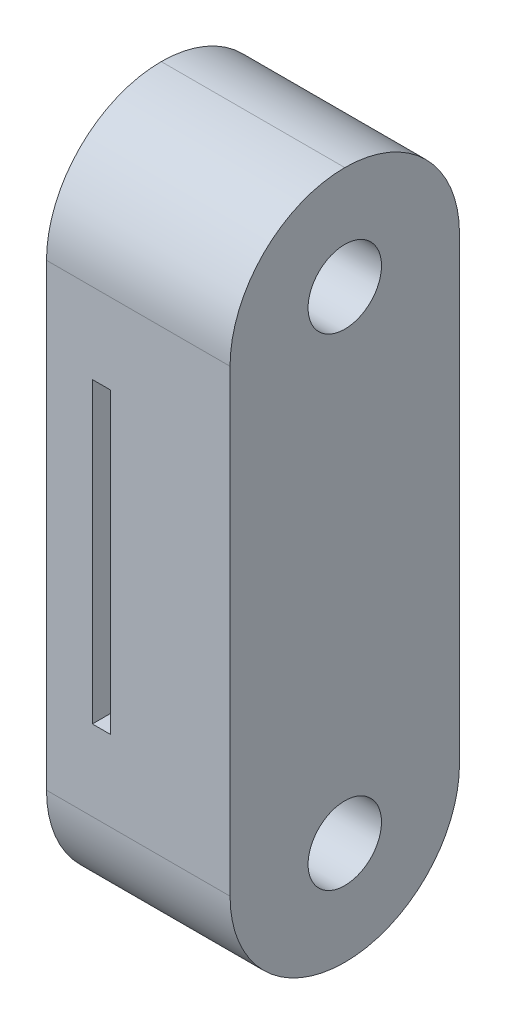
SolidWorks part; units mm, degrees
ref_plane "xy" through (0, 0, 0) normal (0, 0, 1) x (1, 0, 0)
ref_plane "xz" through (0, 0, 0) normal (0, 1, 0) x (1, 0, 0)
ref_plane "yz" through (0, 0, 0) normal (1, 0, 0) x (0, 0, -1)
sketch "Skizze1" plane through (0, 0, 0) normal (0, 0, 1) x (1, 0, 0)
  line L0 (-8, 15) -> (-8, -15)
  line L1 (-8, 15) -> (0, 15)
  line L2 (-8, 0) -> (0, 0) construction
  line L3 (-8, -15) -> (0, -15)
  line L4 (0, 15) -> (0, -15)
  line L5 (0, 6) -> (0, -6) construction
  line L6 (0, 6) -> (0, 15) construction
  line L7 (0, -6) -> (0, -15) construction
  point P9 (0, -10.5)
  point P12 (0, 10.5)
  dimension "D1" = 30
  dimension "D2" = 12
  dimension "D3" = 8
extrude "Aufsatz-Linear austragen1" add sketch "Skizze1" along normal mid plane 10
sketch "Skizze4" plane through (0, 0, 0) normal (1, 0, 0) x (0, 0, -1)
  circle A0 centre (0, 10.5) radius 1.6
  circle A1 centre (0, -10.5) radius 1.6
  dimension "D1" = 3.2
extrude "Schnitt-Linear austragen4" cut sketch "Skizze4" against normal through all
fillet "Verrundung1" radius 5 4 edges at (-4, 15, 5) (-4, 15, -5) (-4, -15, 5) (-4, -15, -5)
sketch "Skizze5" plane through (0, 0, 0) normal (0, 0, 1) x (1, 0, 0)
  line L0 (-8, 15) -> (-8, -15) construction
  line L1 (-5.2, 6.5) -> (-6, 6.5)
  line L2 (-5.2, 6.5) -> (-5.2, -6.5)
  line L3 (-5.2, -6.5) -> (-6, -6.5)
  line L4 (-6, 6.5) -> (-6, -6.5)
  point P4 (-5.2, 0)
  dimension "D1" = 0.8
  dimension "D2" = 13
  dimension "D3" = 2
extrude "Schnitt-Linear austragen5" cut sketch "Skizze5" against normal through all and the other way through all
